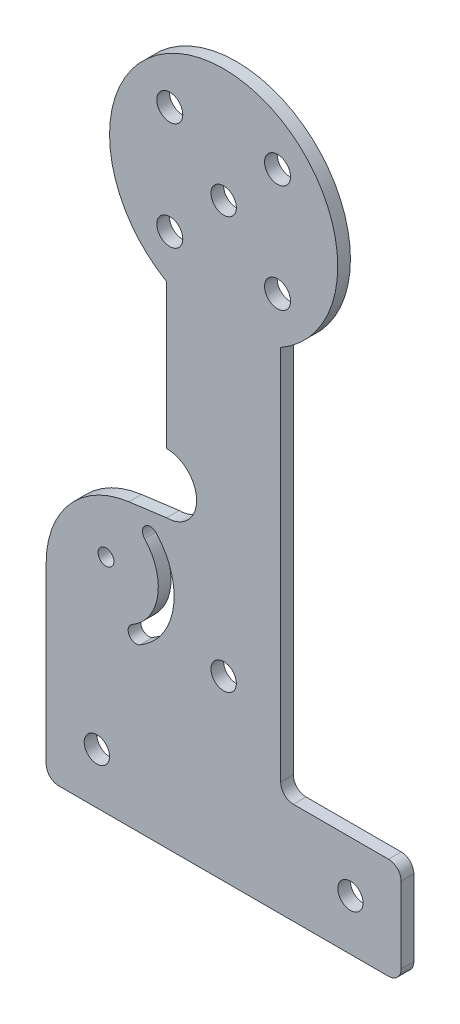
SolidWorks part; units mm, degrees
ref_plane "前视基准面" through (0, 0, 0) normal (0, 0, 1) x (1, 0, 0)
ref_plane "上视基准面" through (0, 0, 0) normal (0, 1, 0) x (1, 0, 0)
ref_plane "右视基准面" through (0, 0, 0) normal (1, 0, 0) x (0, 0, -1)
sketch "草图1" plane through (0, 0, 0) normal (0, 0, 1) x (1, 0, 0)
  line L2 (-13.3404, 23.3177) -> (-13.3404, 108.3177) construction
  line L3 (-13.3404, 108.3177) -> (-7.3404, 108.3177) construction
  line L6 (14.6596, 15.3177) -> (14.6596, 31.3177)
  line L9 (-41.3404, 15.3177) -> (-41.3404, 31.3177)
  line L11 (-41.3404, 31.3177) -> (-22.3404, 31.3177) construction
  line L14 (-33.3404, 23.3177) -> (-13.3404, 23.3177) construction
  line L15 (-13.3404, 23.3177) -> (6.6596, 23.3177) construction
  line L16 (-4.3404, 31.3177) -> (14.6596, 31.3177)
  line L17 (-41.3404, 15.3177) -> (14.6596, 15.3177)
  line L18 (-13.3404, 108.3177) -> (-13.3404, 116.8177) construction
  line L19 (-13.3404, 116.8177) -> (-4.8404, 116.8177) construction
  line L20 (-4.3404, 31.3177) -> (-4.3404, 92.7292)
  line L21 (-22.3404, 31.3177) -> (-22.3404, 92.7292) construction
  line L22 (-22.3404, 92.7292) -> (-22.3404, 69.9222)
  line L23 (-22.3404, 60.4565) -> (-22.3404, 31.3177) construction
  line L27 (-41.3404, 31.3177) -> (-41.3404, 57.9559)
  line L28 (-41.3404, 57.9559) -> (-22.3404, 60.4565)
  circle A4 centre (-33.3404, 23.3177) radius 2
  circle A5 centre (6.6596, 23.3177) radius 2
  circle A9 centre (-13.3404, 108.3177) radius 2
  circle A12 centre (-13.3404, 43.3177) radius 2
  circle A13 centre (-4.8404, 116.8177) radius 2.05
  circle A17 centre (-13.3404, 108.3177) radius 18 construction
  arc A18 (-22.3404, 92.7292) -> (-4.3404, 92.7292) centre (-13.3404, 108.3177) cw
  arc A20 (-22.3404, 69.9222) -> (-22.3404, 60.4565) centre (-22.3404, 65.1893) cw
  circle A23 centre (-31.9023, 50.3177) radius 1.25
  circle A31 centre (-31.9023, 50.3177) radius 9.5 construction
  arc A32 (-24.8954, 56.7327) -> (-27.1601, 42.0859) centre (-31.9023, 50.3177) cw construction
  arc A33 (-26.5362, 41.0028) -> (-23.9734, 57.5768) centre (-31.9023, 50.3177) ccw
  arc A34 (-27.7841, 43.1691) -> (-25.8173, 55.8886) centre (-31.9023, 50.3177) ccw
  arc A35 (-27.7841, 43.1691) -> (-26.5362, 41.0028) centre (-27.1601, 42.0859) ccw
  arc A36 (-23.9734, 57.5768) -> (-25.8173, 55.8886) centre (-24.8954, 56.7327) ccw
  circle A37 centre (-4.8404, 99.8177) radius 2.05
  circle A38 centre (-21.8404, 99.8177) radius 2.05
  circle A39 centre (-21.8404, 116.8177) radius 2.05
  point P31 (-22.5139, 48.866)
  dimension "D5" = 4
  dimension "D6" = 2.5
  dimension "D7" = 4
  dimension "D8" = 65
  dimension "D13" = 19
  dimension "D14" = 27
  dimension "D2" = 20
  dimension "D3" = 8
  dimension "D4" = 8
  dimension "D9" = 8
  dimension "D10" = 20
  dimension "D11" = 20
  dimension "D12" = 8
extrude "凸台-拉伸1" add sketch "草图1" along normal blind 2
fillet "圆角1" radius 2 4 edges at (14.6596, 31.3177, 1) (14.6596, 15.3177, 1) (-41.3404, 15.3177, 1) (-4.3404, 31.3177, 1)
fillet "圆角2" radius 15 1 edges at (-41.3404, 57.9559, 1)
